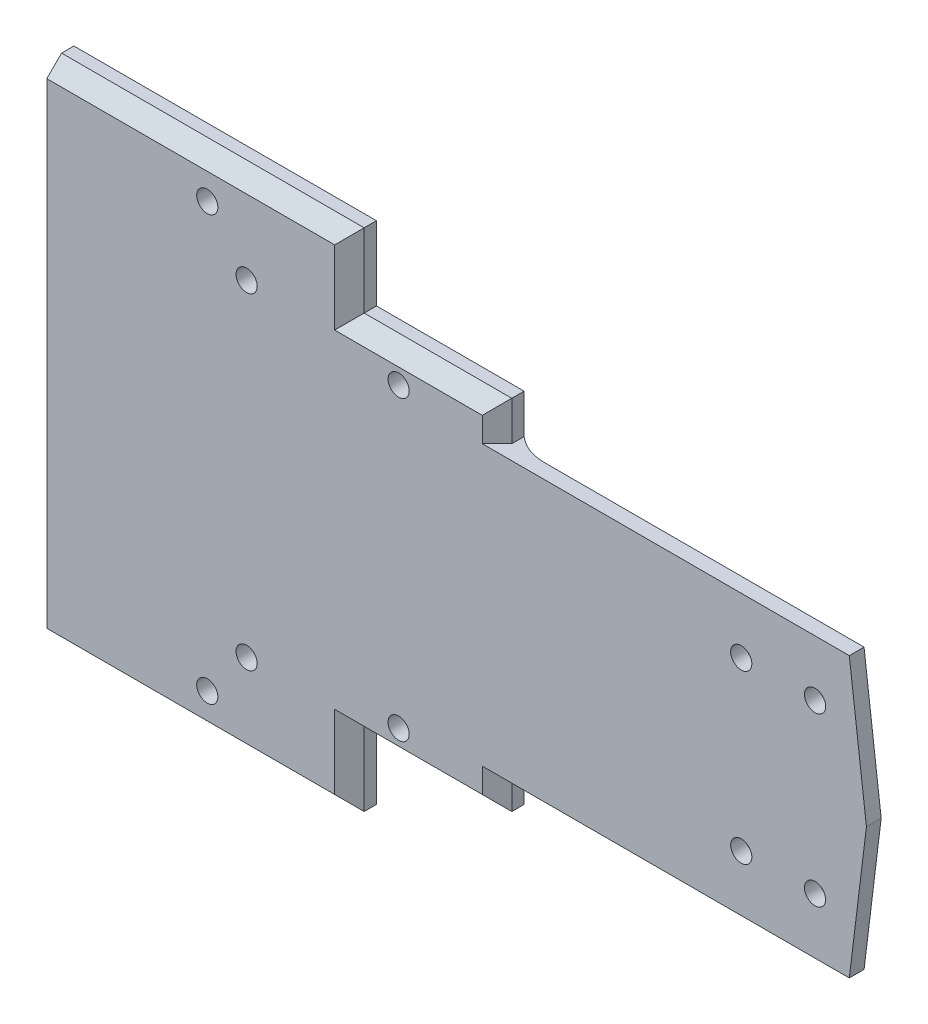
SolidWorks part; units mm, degrees
material "petg 20%"
ref_plane "Front Plane" through (0, 0, 0) normal (0, 0, 1) x (1, 0, 0)
ref_plane "Top Plane" through (0, 0, 0) normal (0, 1, 0) x (1, 0, 0)
ref_plane "Right Plane" through (0, 0, 0) normal (1, 0, 0) x (0, 0, -1)
sketch "Sketch1" plane through (0, 0, 0) normal (0, 0, 1) x (1, 0, 0)
  line L1 (-71.25, 28.37) -> (71.25, 28.37)
  line L2 (-71.25, 28.37) -> (-71.25, -28.37)
  line L3 (-71.25, -28.37) -> (71.25, -28.37)
  line L4 (71.25, 28.37) -> (71.25, -28.37)
  line L5 (-71.25, 28.37) -> (71.25, -28.37) construction
  line L6 (-71.25, -28.37) -> (71.25, 28.37) construction
  point P0 (0, 0)
  dimension "D1" = 142.5
  dimension "D2" = 56.74
extrude "Boss-Extrude1" add sketch "Sketch1" along normal blind 3
sketch "Sketch2" plane through (0, 0, 3) normal (0, 0, 1) x (1, 0, 0)
  line L0 (71.25, 0) -> (67.7716, 28.37)
  line L1 (71.25, -28.37) -> (71.25, 28.37) construction
  line L2 (71.25, 28.37) -> (-71.25, 28.37) construction
  line L3 (71.25, 0) -> (67.7716, -28.37)
  line L4 (-71.25, -28.37) -> (71.25, -28.37) construction
  line L6 (67.7716, 28.37) -> (71.25, 28.37)
  line L7 (71.25, 28.37) -> (71.25, -28.37)
  line L8 (71.25, -28.37) -> (67.7716, -28.37)
  line M3 (71.25, -28.37) -> (71.25, 28.37)
  line M4 (71.25, 28.37) -> (-71.25, 28.37)
  line M6 (-71.25, -28.37) -> (71.25, -28.37)
  dimension "D1" = 166.02
extrude "Cut-Extrude1" cut sketch "Sketch2" against normal through all contours L0 M3 M4 | L3 M3 M6 region at (70.0905, -18.9133, 3) region at (70.0905, 18.9133, 3)
sketch "Sketch3" plane through (0, 0, 3) normal (0, 0, 1) x (1, 0, 0)
  line L0 (-71.25, 28.37) -> (-71.25, -28.37)
  line L1 (-71.25, 28.37) -> (-68.825, 28.37)
  line L2 (-71.25, -28.37) -> (-68.825, -28.37)
  line L3 (-68.825, 28.37) -> (-68.825, -28.37)
  dimension "D1" = 2.425
extrude "Cut-Extrude2" cut sketch "Sketch3" against normal through all contours L0 L1 L3 L2
sketch "Sketch4" plane through (0, 0, 3) normal (0, 0, 1) x (1, 0, 0)
  line L0 (-68.825, 28.37) -> (-3.825, 28.37)
  line L1 (-68.825, 28.37) -> (-68.825, 36.37)
  line L2 (-3.825, 28.37) -> (-3.825, 36.37)
  line L3 (-68.825, 36.37) -> (-3.825, 36.37)
  line L6 (-68.825, -28.37) -> (-3.825, -28.37)
  line L7 (-68.825, -28.37) -> (-68.825, -36.37)
  line L8 (-3.825, -28.37) -> (-3.825, -36.37)
  line L9 (-68.825, -36.37) -> (-3.825, -36.37)
  line L13 (-68.825, 36.37) -> (-3.825, 36.37)
  line L14 (-68.825, 36.37) -> (-68.825, -36.37)
  line L15 (-68.825, -36.37) -> (-3.825, -36.37)
  line L16 (-3.825, 36.37) -> (-3.825, -36.37)
  dimension "D1" = 8
  dimension "D2" = 8
  dimension "D3" = 65
  dimension "D4" = 65
  dimension "D5" = 65
extrude "Boss-Extrude2" add sketch "Sketch4" against normal blind 5.5 contours L16 | L3 L1 L2 | L7 L9 L8 region at (-36.325, 32.37, 3) region at (-36.325, 0, 3) region at (-36.325, -32.37, 3)
fillet "Fillet1" radius 10 1 edges at (-3.825, 0, 0)
fillet "Fillet2" [suppressed] radius 10
sketch "Sketch5" plane through (0, 0, 3) normal (0, 0, 1) x (1, 0, 0)
  circle A0 centre (60.808, 17) radius 2.15
  circle A1 centre (60.808, -17) radius 2.15
  circle A2 centre (45.808, 17) radius 2.15
  circle A3 centre (45.808, -17) radius 2.15
  dimension "D1" = 4.3
  dimension "D3" = 4.3
  dimension "D5" = 4.3
  dimension "D6" = 4.3
  dimension "D8" = 17
  dimension "D9" = 15
  dimension "D10" = 15
  dimension "D2" = 17
  dimension "D4" = 17
  dimension "D7" = 17
extrude "Cut-Extrude3" cut sketch "Sketch5" against normal through all
sketch "Sketch6" [suppressed] plane through (0, 0, 0) normal (0, 0, -1) x (-1, 0, 0)
  circle A0 centre (-45.805, -17) radius 2.05
  circle A1 centre (-60.805, -17) radius 2.05
  circle A2 centre (-45.805, 17) radius 2.05
  circle A3 centre (-60.805, 17) radius 2.05
extrude "Cut-Extrude4" [suppressed] cut sketch "Sketch6" against normal blind 10
sketch "Sketch7" [suppressed] plane through (0, 0, 3) normal (0, 0, 1) x (1, 0, 0)
  line L1 (-68.825, 36.37) -> (-33.825, 36.37)
  line L2 (-68.825, 36.37) -> (-68.825, 51.37)
  line L3 (-68.825, 51.37) -> (-33.825, 51.37)
  line L4 (-33.825, 36.37) -> (-33.825, 51.37)
  line L5 (-68.825, -36.37) -> (-33.825, -36.37)
  line L6 (-68.825, -36.37) -> (-68.825, -51.37)
  line L7 (-68.825, -51.37) -> (-33.825, -51.37)
  line L8 (-33.825, -36.37) -> (-33.825, -51.37)
  dimension "D1" = 15
  dimension "D2" = 35
  dimension "D3" = 15
  dimension "D4" = 35
extrude "Boss-Extrude3" [suppressed] add sketch "Sketch7" against normal up to surface (4.11 mm away)
sketch "Sketch9" [suppressed] plane through (0, 0, 3) normal (0, 0, 1) x (1, 0, 0)
  line L0 (-68.825, 51.37) -> (-68.825, -51.37)
  line L1 (-68.825, 51.37) -> (-95.325, 51.37)
  line L2 (-68.825, -51.37) -> (-95.325, -51.37)
  line L3 (-95.325, 51.37) -> (-95.325, -51.37)
  dimension "D1" = 26.5
extrude "Boss-Extrude4" [suppressed] add sketch "Sketch9" against normal up to surface (4.11 mm away)
sketch "Sketch10" plane through (0, 0, 3) normal (0, 0, 1) x (1, 0, 0)
  line L0 (-68.825, 36.37) -> (-33.825, 36.37)
  line L2 (-33.825, 36.37) -> (-33.825, 51.37)
  line L3 (-68.825, 51.37) -> (-33.825, 51.37)
  line L4 (-68.825, 36.37) -> (-3.825, 36.37) construction
  line L5 (-68.825, -36.37) -> (-33.825, -36.37)
  line L7 (-33.825, -36.37) -> (-33.825, -51.37)
  line L8 (-68.825, -51.37) -> (-33.825, -51.37)
  line L9 (-68.825, -36.37) -> (-3.825, -36.37) construction
  line L10 (-68.825, 36.37) -> (-68.825, -36.37)
  line L11 (-68.825, 51.37) -> (-95.325, 51.37)
  line L12 (-68.825, -51.37) -> (-95.325, -51.37)
  line L13 (-95.325, 51.37) -> (-95.325, -51.37)
  dimension "D1" = 15
  dimension "D2" = 15
  dimension "D3" = 35
  dimension "D4" = 35
  dimension "D5" = 26.5
extrude "Boss-Extrude5" add sketch "Sketch10" against normal blind 5.5
chamfer "Chamfer6" distance 3 angle 45 8 edges at (-3.825, 32.37, 3) (-18.825, 36.37, 3) (-33.825, 43.87, 3) (-64.575, 51.37, 3) (-3.825, -32.37, 3) (-18.825, -36.37, 3) (-33.825, -43.87, 3) (-64.575, -51.37, 3)
chamfer "Chamfer7" [suppressed] distance 3 angle 45
sketch "Sketch11" plane through (0, 0, 3) normal (0, 0, 1) x (1, 0, 0)
  circle A1 centre (-62.7149, -43.08) radius 2.15
  circle A2 centre (-54.7149, -33.1839) radius 2.15
  circle A3 centre (-23.8214, -30.1967) radius 2.15
  dimension "D1" = 4.3
  dimension "D3" = 4.3
  dimension "D4" = 4.3
extrude "Cut-Extrude5" cut sketch "Sketch11" against normal through all
sketch "Sketch12" [suppressed] plane through (0, 0, -1.11) normal (0, 0, -1) x (-1, 0, 0)
  circle A1 centre (62.7179, 43.08) radius 2.05
  circle A2 centre (54.7179, 33.1839) radius 2.05
  circle A3 centre (23.8244, 30.1967) radius 2.05
extrude "Cut-Extrude6" [suppressed] cut sketch "Sketch12" against normal through all
ref_plane "Plane1" [suppressed] through (0, 0, 0) normal (0, 1, 0) x (1, 0, 0)
mirror "Mirror1" [suppressed] about plane through (0, 0, 0) normal (0, 1, 0)
ref_plane "Plane2" through (0, 0, 0) normal (0, 1, 0) x (1, 0, 0)
mirror "Mirror2" about plane through (0, 0, 0) normal (0, 1, 0) of "Cut-Extrude5"
